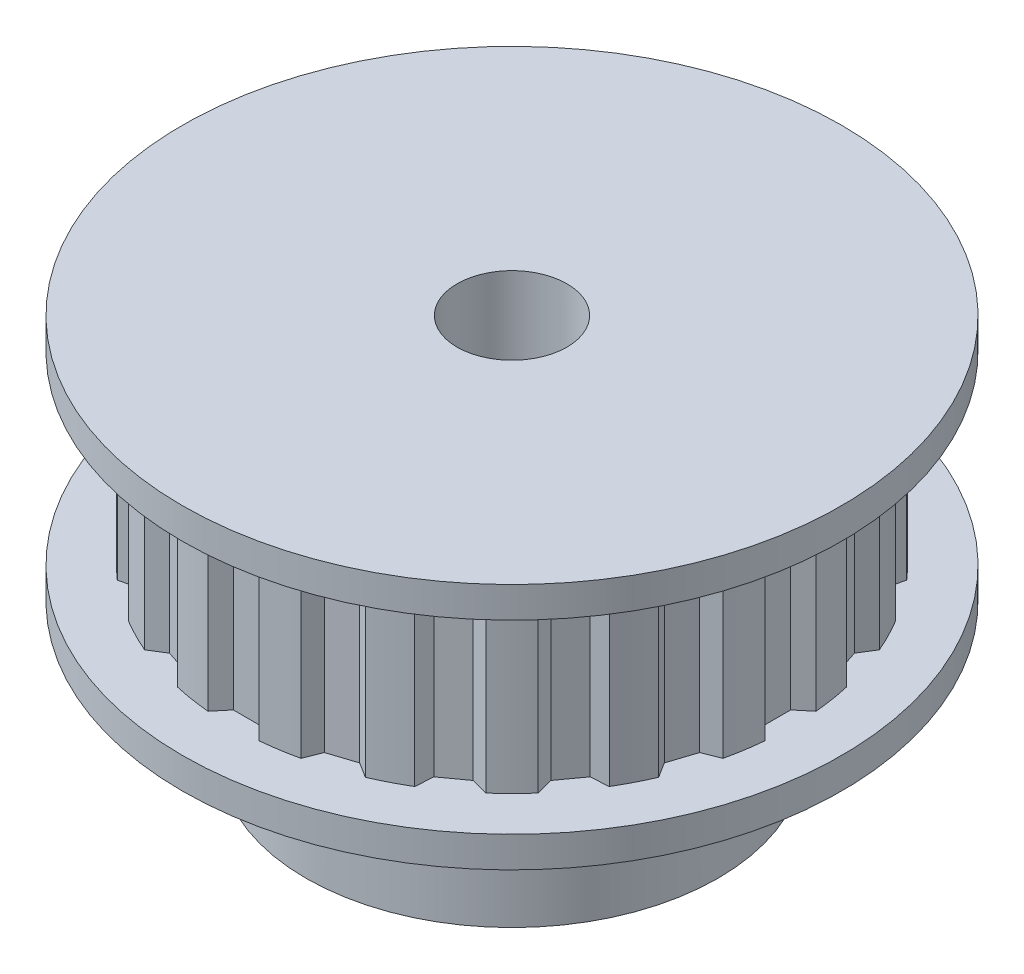
SolidWorks part; units mm, degrees
ref_plane "Front Plane" through (0, 0, 0) normal (0, 0, 1) x (1, 0, 0)
ref_plane "Top Plane" through (0, 0, 0) normal (0, 1, 0) x (1, 0, 0)
ref_plane "Right Plane" through (0, 0, 0) normal (1, 0, 0) x (0, 0, -1)
sketch "Sketch1" plane through (0, 0, 0) normal (0, 1, 0) x (1, 0, 0)
  circle A0 centre (0, 0) radius 19.05
  circle A1 centre (0, 0) radius 3.175
extrude "Boss-Extrude1" add sketch "Sketch1" along normal blind 14.2875
ref_plane "Midplane" through (0, 7.1437, 0) normal (0, 1, 0) x (-1, 0, 0)
sketch "Sketch5" plane through (0, 7.1437, 0) normal (0, 1, 0) x (-1, 0, 0)
  circle A0 centre (0, 0) radius 16.1671
  circle A1 centre (0, 0) radius 20.2205
extrude "Cut-Extrude2" cut sketch "Sketch5" against normal mid plane 10.7188
sketch "Sketch3" plane through (0, 7.1437, 0) normal (0, 1, 0) x (-1, 0, 0)
  line L0 (-2.6101, 17.4628) -> (2.6101, 17.4628)
  line L1 (2.6101, 17.4628) -> (0.8101, 15.3003)
  line L2 (0.8101, 15.3003) -> (-0.8101, 15.3003)
  line L3 (0, 15.3003) -> (0, 20.2135) construction
  line L4 (-2.6101, 17.4628) -> (-0.8101, 15.3003)
  point P8 (0, 17.4628)
extrude "Cut-Extrude1" cut sketch "Sketch3" against normal mid plane 10.7188
pattern_circular "CirPattern1" count 20 over 360 about axis through (0, 14.2875, 0) along (0, 1, 0) of "Cut-Extrude1"
sketch "Sketch6" plane through (0, 0, 0) normal (0, -1, 0) x (1, 0, 0)
  circle A0 centre (0, 0) radius 11.9062
  circle A1 centre (0, 0) radius 3.175
extrude "Boss-Extrude2" add sketch "Sketch6" along normal blind 7.9375
sketch "Sketch7" plane through (0, 0, 0) normal (0, 0, 1) x (1, 0, 0)
  circle A0 centre (0, -3.8668) radius 0.8255
extrude "Cut-Extrude3" cut sketch "Sketch7" against normal through all and the other way through all
